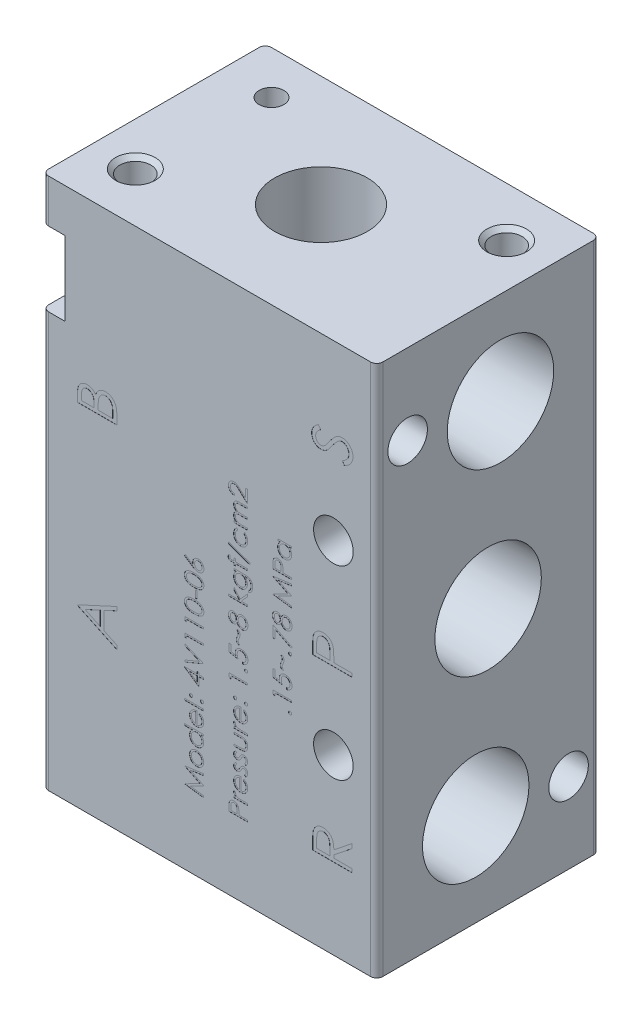
SolidWorks part; units mm, degrees
material "6061-T6 (SS)"
ref_plane "Front Plane" through (0, 0, 0) normal (0, 0, 1) x (1, 0, 0)
ref_plane "Top Plane" through (0, 0, 0) normal (0, 1, 0) x (1, 0, 0)
ref_plane "Right Plane" through (0, 0, 0) normal (1, 0, 0) x (0, 0, -1)
sketch "BaseS" plane through (0, 0, 0) normal (0, 1, 0) x (1, 0, 0)
  line L1 (-13.5, 9) -> (13.5, 9)
  line L2 (-13.5, 9) -> (-13.5, -9)
  line L3 (-13.5, -9) -> (13.5, -9)
  line L4 (13.5, 9) -> (13.5, -9)
  line L5 (-13.5, 9) -> (13.5, -9) construction
  line L6 (-13.5, -9) -> (13.5, 9) construction
  point P0 (0, 0)
  dimension "Length" = 27
  dimension "Width" = 18
extrude "Base" add sketch "BaseS" along normal mid plane 43
hole_wizard "M3x0.5 Tapped Hole1" positions "Sketch4" profile "Sketch5" tap size "M3x0.5" standard "ANSI Metric"
sketch "Sketch4" plane through (0, 21.5, 0) normal (0, 1, 0) x (1, 0, 0)
  line L2 (-13.5, 9) -> (-13.5, -9) construction
  line L4 (-10, -5) -> (-10, -9) construction
  line L6 (-10, -5) -> (-13.5, -5) construction
  line L11 (10, 5) -> (13.5, 5) construction
  line L12 (13.5, -9) -> (13.5, 9) construction
  line L14 (-13.5, -9) -> (13.5, -9) construction
  line L15 (10, 5) -> (10, 9) construction
  line L16 (13.5, 9) -> (-13.5, 9) construction
  point P0 (10, 5)
  point P7 (-10, -5)
  dimension "XLoc" = 3.5
  dimension "YLoc" = 4
  dimension "RefX" = 20
  dimension "RefY" = 10
sketch "Sketch5" plane through (10, 21.5, -5) normal (1, 0, 0) x (0, 0, 1)
  line L0 (0, 0) -> (0, 4.7511)
  line L1 (0, 4.7511) -> (1.25, 4)
  line L2 (1.25, 4) -> (1.25, 0.35)
  line L3 (1.25, 0.35) -> (1.6, 0)
  line L5 (1.6, 0) -> (0, 0)
  line L6 (-1.25, 0.35) -> (-1.6, 0) construction
  line L10 (0, 4.7511) -> (-1.25, 4) construction
  line L11 (0, -6.35) -> (0, 107.95) construction
  dimension "Tap Drill Dia." = 2.5
  dimension "Tap Drill Depth" = 4
  dimension "Near C'Sink Dia." = 3.2
  dimension "Near C'Sink Angle" = 90
  dimension "Drill Angle" = 118
cosmetic thread "Hole Thread1" parameters "D1"=4, "D2"=3
cosmetic thread "Hole Thread2" parameters "D1"=4, "D2"=3
hole_wizard "M3x0.5 Tapped Hole2" positions "Sketch12" profile "Sketch13" tap size "M3x0.5" standard "ANSI Metric"
sketch "Sketch12" plane through (0, -21.5, 0) normal (0, -1, 0) x (-1, 0, 0)
  line L1 (13.5, 9) -> (13.5, -9) construction
  line L3 (-13.5, 9) -> (13.5, 9) construction
  line L4 (10, 5) -> (13.5, 5) construction
  line L6 (10, 5) -> (10, 9) construction
  line L8 (-13.5, -5) -> (-10, -5) construction
  line L9 (-13.5, -9) -> (-13.5, 9) construction
  line L10 (-10, -5) -> (-10, -9) construction
  line L11 (13.5, -9) -> (-13.5, -9) construction
  point P0 (10, 5)
  point P14 (-10, -5)
  dimension "XDim" = 3.5
  dimension "YDim" = 4
  dimension "RefHeight" = 10
  dimension "RefWidth" = 20
sketch "Sketch13" plane through (-10, -21.5, -5) normal (1, 0, 0) x (0, 0, -1)
  line L0 (0, 0) -> (0, 4.7511)
  line L1 (0, 4.7511) -> (1.25, 4)
  line L2 (1.25, 4) -> (1.25, 0)
  line L5 (1.25, 0) -> (0, 0)
  line L10 (0, 4.7511) -> (-1.25, 4) construction
  line L11 (0, -6.35) -> (0, 107.95) construction
  dimension "Tap Drill Dia." = 2.5
  dimension "Tap Drill Depth" = 4
  dimension "Drill Angle" = 118
cosmetic thread "Hole Thread3" parameters "D1"=4, "D2"=3
cosmetic thread "Hole Thread4" parameters "D1"=4, "D2"=3
hole_wizard " Clearance Hole2" positions "Sketch14" profile "Sketch15" hole size "M3" standard "ANSI Metric" end condition through all
sketch "Sketch14" plane through (0, 0, 9) normal (0, 0, 1) x (1, 0, 0)
  line L1 (-13.5, -21.5) -> (13.5, -21.5) construction
  line L2 (13.5, 21.5) -> (13.5, -21.5) construction
  point P0 (10, -7.5)
  dimension "D1" = 3.5
  dimension "YDim" = 14
sketch "Sketch15" plane through (10, -7.5, 9) normal (1, 0, 0) x (0, -1, 0)
  line L0 (0, 0) -> (0, 18)
  line L1 (0, 18) -> (1.6, 18)
  line L2 (1.6, 18) -> (1.6, 0)
  line L5 (1.6, 0) -> (0, 0)
  line L11 (0, -6.35) -> (0, 107.95) construction
  dimension "Thru Hole Dia." = 3.2
  dimension "Thru Hole Depth" = 18
mirror "Mirror1" about plane through (0, 0, 0) normal (0, 1, 0) of " Clearance Hole2"
sketch "TopLocatingBoreS" plane through (0, 21.5, 0) normal (0, 1, 0) x (1, 0, 0)
  line L0 (-13.5, 9) -> (-13.5, -9) construction
  line L1 (13.5, 9) -> (-13.5, 9) construction
  circle A0 centre (-9.5, 5.5) radius 1
  dimension "Dia" = 2
  dimension "XDim" = 4
  dimension "YDim" = 3.5
extrude "TopLocatingBore" cut sketch "TopLocatingBoreS" against normal blind 22
sketch "BottomLocatingBoreS" plane through (0, -21.5, 0) normal (0, -1, 0) x (1, 0, 0)
  line L0 (-13.5, 9) -> (13.5, 9) construction
  line L1 (-13.5, -9) -> (-13.5, 9) construction
  circle A0 centre (-9.5, 5) radius 1
  dimension "Dia" = 2
  dimension "YDim" = 4
  dimension "XDim" = 4
extrude "BottomLocatingBore" cut sketch "BottomLocatingBoreS" against normal blind 15
hole_wizard "M3 Clearance Hole1" positions "Sketch18" profile "Sketch19" hole size "M3" standard "ANSI Metric" end condition through all
sketch "Sketch18" plane through (-13.5, 0, 0) normal (-1, 0, 0) x (0, 0, 1)
  line L0 (-9, 21.5) -> (9, 21.5) construction
  line L1 (9, 21.5) -> (9, -21.5) construction
  line L2 (-9, 21.5) -> (-9, -21.5) construction
  line L3 (-9, -21.5) -> (9, -21.5) construction
  point P0 (6.5, 15)
  point P7 (-6.5, -15)
  dimension "YDim" = 6.5
  dimension "XDim" = 2.5
  dimension "XDim2" = 2.5
  dimension "YDim2" = 6.5
sketch "Sketch19" plane through (-13.5, 15, 6.5) normal (0, 1, 0) x (0, 0, 1)
  line L0 (0, 0) -> (0, 27)
  line L1 (0, 27) -> (1.6, 27)
  line L2 (1.6, 27) -> (1.6, 0)
  line L5 (1.6, 0) -> (0, 0)
  line L11 (0, -6.35) -> (0, 107.95) construction
  dimension "Thru Hole Dia." = 3.2
  dimension "Thru Hole Depth" = 27
sketch "SlotS" plane through (-13.5, 0, 0) normal (-1, 0, 0) x (0, 0, 1)
  line L0 (6.5, 15) -> (9, 15) construction
  line L4 (6.5, 18) -> (9, 18)
  line L5 (6.5, 12) -> (9, 12)
  line L6 (9, 12) -> (9, 18)
  line L7 (9, 21.5) -> (9, -21.5) construction
  line L8 (-6.5, -15) -> (-9, -15) construction
  line L9 (-6.5, -18) -> (-9, -18)
  line L10 (-6.5, -12) -> (-9, -12)
  line L11 (-9, 21.5) -> (-9, -21.5) construction
  line L12 (-9, -18) -> (-9, -12)
  arc A2 (6.5, 18) -> (6.5, 12) centre (6.5, 15) ccw
  arc A4 (-6.5, -18) -> (-6.5, -12) centre (-6.5, -15) ccw
  circle A6 centre (-6.5, -15) radius 1.6 construction
  dimension "Width" = 6
extrude "Slot" cut sketch "SlotS" against normal blind 1.8
sketch "PortPRSLocations" plane through (13.5, 0, 0) normal (1, 0, 0) x (0, 0, -1)
  line L0 (-9, 21.5) -> (-9, -21.5) construction
  line L1 (-9, -21.5) -> (9, -21.5) construction
  line L2 (9, 21.5) -> (9, -21.5) construction
  line L3 (-9, 21.5) -> (9, 21.5) construction
  point P0 (-1, -14)
  point P5 (0, 0)
  point P6 (1, 14)
  dimension "BLXDim" = 8
  dimension "BLYDim" = 7.5
  dimension "TRXDim" = 8
  dimension "TRYDim" = 7.5
sketch "PortABLocations" plane through (-13.5, 0, 0) normal (-1, 0, 0) x (0, 0, 1)
  line L3 (-9, -21.5) -> (9, -21.5) construction
  line L4 (-9, 21.5) -> (9, 21.5) construction
  line L5 (9, 21.5) -> (9, 18) construction
  line L6 (-9, -18) -> (-9, -21.5) construction
  point P0 (1.5, 8)
  point P1 (-1.5, -8)
  dimension "D1" = 13.5
  dimension "D2" = 13.5
  dimension "D3" = 7.5
  dimension "D4" = 7.5
hole_wizard "1/8 Rc Tapped Hole1" positions "Sketch22" profile "Sketch24" size "1/8" standard "ISO"
sketch "Sketch22" plane through (13.5, 0, 0) normal (1, 0, 0) x (0, 0, -1)
  point P0 (1, 14)
  point P4 (0, 0)
  point P7 (-1, -14)
sketch "Sketch24" plane through (13.5, 14, -1) normal (0, 1, 0) x (0, 0, -1)
  line L0 (0, 0) -> (0, 10.9034)
  line L1 (4, 8.5) -> (0, 10.9034)
  line L2 (-4, 8.5) -> (0, 10.9034) construction
  line L3 (4, 8.5) -> (4, 7.5)
  line L4 (4, 7.5) -> (4.0659, 7.5)
  line L5 (4.0659, 7.5) -> (4.3, 0)
  line L6 (-4.0659, 7.5) -> (-4.3, 0) construction
  line L7 (4.3, 0) -> (0, 0)
  line L8 (0, -6.35) -> (0, 107.95) construction
  line L11 (-4, 7.5) -> (-4.0659, 7.5) construction
  dimension "Tap Drill Dia." = 8
  dimension "Tap Drill Depth" = 8.5
  dimension "Thread Dia." = 8.6
  dimension "Thread Angle" = 3.576
  dimension "Thread Depth" = 7.5
  dimension "Drill Angle" = 118
ref_plane "PortBottomPRS" through (5, 0, 0) normal (1, 0, 0) x (0, 0, -1)
sketch "PortPRSHolesCoverS" plane through (5, 0, 0) normal (1, 0, 0) x (0, 0, -1)
  circle A0 centre (1, 14) radius 4.0659 construction
  circle A1 centre (1, 14) radius 4.0659
  circle A2 centre (-1, -14) radius 4.0659 construction
  circle A3 centre (0, 0) radius 4.0659 construction
  circle A4 centre (-1, -14) radius 4.0659
  circle A5 centre (0, 0) radius 4.0659
extrude "PortPRSHolesCover" add sketch "PortPRSHolesCoverS" against normal blind 2
hole_wizard "1/8 Rc Tapped Hole2" positions "Sketch27" profile "Sketch28" size "1/8" standard "BSI"
sketch "Sketch27" plane through (-13.5, 0, 0) normal (-1, 0, 0) x (0, 0, 1)
  point P0 (-1.5, -8)
  point P3 (1.5, 8)
sketch "Sketch28" plane through (-13.5, -8, -1.5) normal (0, 1, 0) x (0, 0, 1)
  line L0 (0, 0) -> (0, 10.9034)
  line L1 (4, 8.5) -> (0, 10.9034)
  line L2 (-4, 8.5) -> (0, 10.9034) construction
  line L3 (4, 8.5) -> (4, 7.5)
  line L4 (4, 7.5) -> (4.0659, 7.5)
  line L5 (4.0659, 7.5) -> (4.3, 0)
  line L6 (-4.0659, 7.5) -> (-4.3, 0) construction
  line L7 (4.3, 0) -> (0, 0)
  line L8 (0, -6.35) -> (0, 107.95) construction
  line L11 (-4, 7.5) -> (-4.0659, 7.5) construction
  dimension "Tap Drill Dia." = 8
  dimension "Tap Drill Depth" = 8.5
  dimension "Thread Dia." = 8.6
  dimension "Thread Angle" = 3.576
  dimension "Thread Depth" = 7.5
  dimension "Drill Angle" = 118
ref_plane "PortBottomAB" through (-5, 0, 0) normal (-1, 0, 0) x (0, 0, 1)
sketch "PortABHolesCoverS" plane through (-5, 0, 0) normal (-1, 0, 0) x (0, 0, 1)
  circle A0 centre (-1.5, -8) radius 4 construction
  circle A1 centre (1.5, 8) radius 4 construction
  circle A2 centre (-1.5, -8) radius 4
  circle A3 centre (1.5, 8) radius 4
extrude "PortABHolesCover" add sketch "PortABHolesCoverS" against normal up to vertex (5 mm away) up to point (0, -2.5966, 8)
sketch "BoreS" plane through (0, 21.5, 0) normal (0, 1, 0) x (1, 0, 0)
  circle A0 centre (0, 0) radius 3.75
  dimension "D2" = 7.5
extrude "Bore" cut sketch "BoreS" against normal through all
sketch "PortPRSSlotsS" plane through (5, 0, 0) normal (1, 0, 0) x (0, 0, -1)
  line L0 (-1.5, 13.65) -> (3.5, 13.65) construction
  line L1 (-1.5, 14.9) -> (3.5, 14.9)
  line L2 (-1.5, 12.4) -> (3.5, 12.4)
  line L3 (-3.5, -13.65) -> (1.5, -13.65) construction
  line L4 (-3.5, -12.4) -> (1.5, -12.4)
  line L5 (-3.5, -14.9) -> (1.5, -14.9)
  line L6 (1, 10) -> (1, 12.4) construction
  line L7 (-1, -12.4) -> (-1, -10) construction
  line L8 (-2, 0) -> (2, 0) construction
  line L9 (-2, 1.75) -> (2, 1.75)
  line L10 (-2, -1.75) -> (2, -1.75)
  arc A0 (-1.5, 14.9) -> (-1.5, 12.4) centre (-1.5, 13.65) ccw
  arc A1 (3.5, 12.4) -> (3.5, 14.9) centre (3.5, 13.65) ccw
  arc A2 (-3.5, -12.4) -> (-3.5, -14.9) centre (-3.5, -13.65) ccw
  arc A3 (1.5, -14.9) -> (1.5, -12.4) centre (1.5, -13.65) ccw
  circle A4 centre (1, 14) radius 4 construction
  circle A5 centre (1, 14) radius 4 construction
  circle A6 centre (-1, -14) radius 4 construction
  arc A7 (-2, 1.75) -> (-2, -1.75) centre (-2, 0) ccw
  arc A8 (2, -1.75) -> (2, 1.75) centre (2, 0) ccw
  point P2 (1, 13.65)
  point P9 (-1, -13.65)
  point P26 (0, 0)
  dimension "D1" = 2.5
  dimension "D2" = 5
  dimension "D3" = 2.4
  dimension "D4" = 3.5
  dimension "D5" = 4
extrude "PortPRSSlots" cut sketch "PortPRSSlotsS" against normal up to surface (5 mm away) up to plane "Right Plane"
sketch "PortABSlotsS" plane through (-5, 0, 0) normal (-1, 0, 0) x (0, 0, 1)
  line L0 (-3.25, -7.2) -> (0.25, -7.2) construction
  line L1 (-3.25, -6) -> (0.25, -6)
  line L2 (-3.25, -8.4) -> (0.25, -8.4)
  line L3 (-0.25, 7.2) -> (3.25, 7.2) construction
  line L4 (-0.25, 8.4) -> (3.25, 8.4)
  line L5 (-0.25, 6) -> (3.25, 6)
  line L6 (-1.5, -6) -> (-1.5, -4) construction
  line L7 (1.5, 4) -> (1.5, 6) construction
  arc A0 (-3.25, -6) -> (-3.25, -8.4) centre (-3.25, -7.2) ccw
  arc A1 (0.25, -8.4) -> (0.25, -6) centre (0.25, -7.2) ccw
  arc A2 (-0.25, 8.4) -> (-0.25, 6) centre (-0.25, 7.2) ccw
  arc A3 (3.25, 6) -> (3.25, 8.4) centre (3.25, 7.2) ccw
  circle A4 centre (-1.5, -8) radius 4 construction
  circle A5 centre (-1.5, -8) radius 4 construction
  circle A6 centre (1.5, 8) radius 4 construction
  point P2 (-1.5, -7.2)
  point P8 (1.5, 7.2)
  dimension "D1" = 2.4
  dimension "D2" = 3.5
  dimension "D3" = 2
extrude "PortABSlots" cut sketch "PortABSlotsS" against normal up to surface (5 mm away) up to plane "Right Plane"
sketch "PortSmoothingS" plane through (0, 0, 0) normal (0, 0, 1) x (1, 0, 0)
  line L0 (5, 14.9) -> (5, 12.4)
  line L2 (-5, -6) -> (-3.75, -6)
  line L3 (5, 14.9) -> (3.75, 14.9)
  line L4 (3.75, 14.9) -> (3.75, 12.4)
  line L5 (3.75, 12.4) -> (5, 12.4)
  line L7 (0, 0) -> (0, 21.5) construction
  line L8 (-13.5, 21.5) -> (13.5, 21.5) construction
  line L9 (-5, -6) -> (-5, -8.4)
  line L10 (3.75, 1.75) -> (5, 1.75)
  line L11 (3.75, 1.75) -> (3.75, -1.75)
  line L12 (3.75, -1.75) -> (5, -1.75)
  line L13 (5, 1.75) -> (5, -1.75)
  line L14 (-5, -8.4) -> (-3.75, -8.4)
  line L15 (-3.75, -6) -> (-3.75, -8.4)
  line L16 (-5, 8.4) -> (-3.75, 8.4)
  line L17 (-5, 8.4) -> (-5, 6)
  line L18 (-5, 6) -> (-3.75, 6)
  line L19 (-3.75, 8.4) -> (-3.75, 6)
  line L20 (5, -12.5) -> (3.75, -12.5)
  line L21 (5, -12.5) -> (5, -14.9)
  line L22 (5, -14.9) -> (3.75, -14.9)
  line L24 (3.75, -12.5) -> (3.75, -14.9)
  line L25 (-3.75, 21.5) -> (-3.75, 8.4) construction
  point P8 (4.563, -15.0536)
  point P10 (3.2968, 14.9)
  point P11 (-2.7496, 8.4)
revolve "PortSmoothing" cut sketch "PortSmoothingS" angle 360 about L7
sketch "PartNameS" plane through (0, 0, 9) normal (0, 0, 1) x (1, 0, 0)
  line L0 (-0.5, -17) -> (-0.5, 21.5) construction
  line L2 (-13.5, 21.5) -> (13.5, 21.5) construction
  line L3 (13.5, 21.5) -> (13.5, -21.5) construction
  line L4 (-13.5, -21.5) -> (13.5, -21.5) construction
  text T0 "  Model: 4V110-06\r\n  Pressure: 1.5~8 kgf/cm2\r\n                  .15~.78 MPa\r\n" font "Century Gothic" height 1.5
  dimension "D1" = 14
  dimension "D2" = 4.5
extrude "PartName" cut sketch "PartNameS" against normal blind 0.01
sketch "PortsPRSLettersS" plane through (0, 0, 9) normal (0, 0, 1) x (1, 0, 0)
  line L0 (11.5, -21.5) -> (11.5, 21.5) construction
  line L1 (-13.5, -21.5) -> (13.5, -21.5) construction
  line L2 (-13.5, 21.5) -> (13.5, 21.5) construction
  line L3 (-13.5, -21.5) -> (13.5, -21.5) construction
  line L4 (13.5, 21.5) -> (13.5, -21.5) construction
  text T0 "     R         P          S"
  dimension "Height" = 2
extrude "PortsPRSLetters" cut sketch "PortsPRSLettersS" against normal blind 0.01
sketch "PortsABLettersS" plane through (0, 0, 9) normal (0, 0, 1) x (1, 0, 0)
  line L0 (-7.5, -21.5) -> (-7.5, 21.5) construction
  line L1 (-13.5, -21.5) -> (13.5, -21.5) construction
  line L2 (-13.5, 21.5) -> (13.5, 21.5) construction
  line L3 (-13.5, 12) -> (-13.5, -21.5) construction
  text T0 "A          B"
  dimension "Height" = 6
extrude "PortsABLetters" cut sketch "PortsABLettersS" against normal up to surface (0.01 mm away) up to face at (9.2857, -14.1834, 8.99)
fillet "BodyF" radius 0.5 6 edges at (-13.5, 19.75, 9) (-13.5, -4.75, 9) (-13.5, -19.75, -9) (-13.5, 4.75, -9) (13.5, 0, -9) (13.5, 0, 9)
